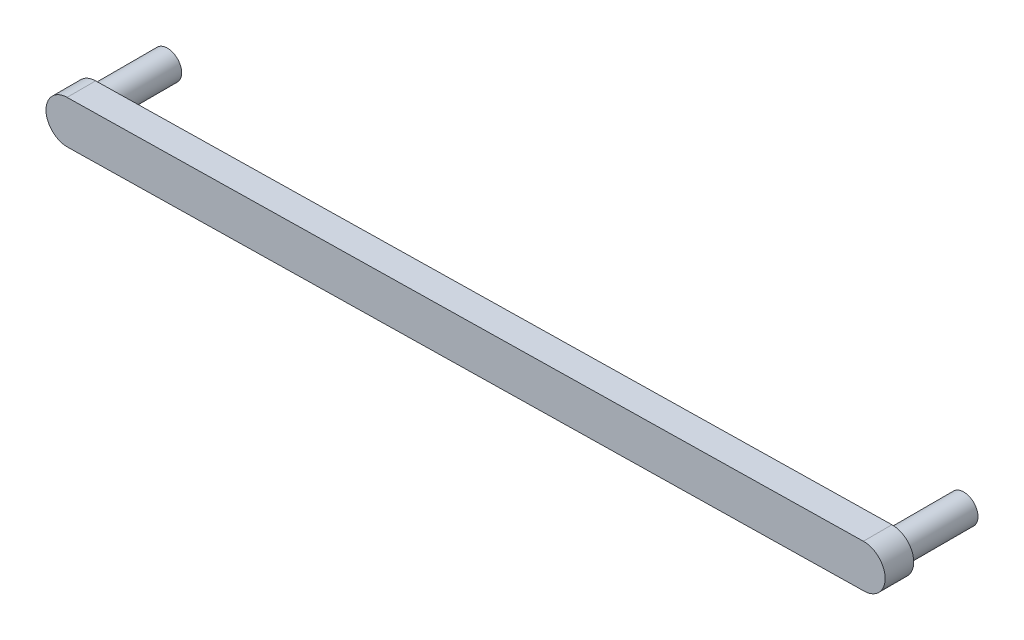
SolidWorks part; units mm, degrees
ref_plane "Front Plane" through (0, 0, 0) normal (0, 0, 1) x (1, 0, 0)
ref_plane "Top Plane" through (0, 0, 0) normal (0, 1, 0) x (1, 0, 0)
ref_plane "Right Plane" through (0, 0, 0) normal (1, 0, 0) x (0, 0, -1)
sketch "Sketch1" plane through (0, 0, 0) normal (0, 0, 1) x (1, 0, 0)
  line L0 (0, -15) -> (55.7532, -14.0368) construction
  line L1 (-0.0259, -13.5002) -> (55.7273, -12.5371)
  line L2 (0.0259, -16.4998) -> (55.7791, -15.5366)
  arc A0 (-0.0259, -13.5002) -> (0.0259, -16.4998) centre (0, -15) ccw
  arc A1 (55.7791, -15.5366) -> (55.7273, -12.5371) centre (55.7532, -14.0368) ccw
  circle A2 centre (0, -15) radius 1
  circle A3 centre (55.7532, -14.0368) radius 1
  point P4 (27.8766, -14.5184)
  dimension "D1" = 1.5
  dimension "D2" = 2
  dimension "D3" = 2
extrude "Boss-Extrude1" add sketch "Sketch1" along normal blind 2 contours L2 A1 L1 A0
extrude "Boss-Extrude2" add sketch "Sketch1<3>" against normal blind 5 contours A2 | A3
sketch "Sketch1<3>" plane through (0, 0, 0) normal (0, 0, 1) x (1, 0, 0) same geometry as "Sketch1"
